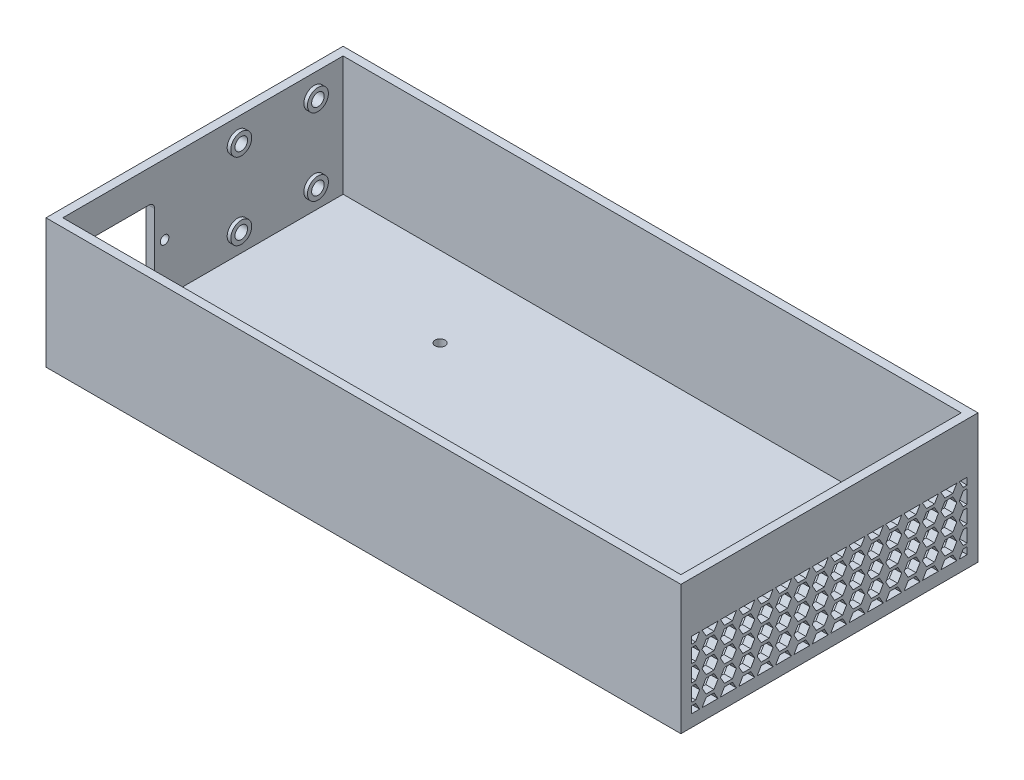
SolidWorks part; units mm, degrees
ref_plane "Front Plane" through (0, 0, 0) normal (0, 0, 1) x (1, 0, 0)
ref_plane "Top Plane" through (0, 0, 0) normal (0, 1, 0) x (1, 0, 0)
ref_plane "Right Plane" through (0, 0, 0) normal (1, 0, 0) x (0, 0, -1)
sketch "Sketch1" plane through (0, 0, 0) normal (0, 1, 0) x (1, 0, 0)
  line L0 (0, 1) -> (216, 1)
  line L1 (0, 0) -> (215, 0)
  line L3 (0, -115) -> (215, -115)
  line L4 (215, 0) -> (215, -115)
  line L5 (0, 0) -> (-41, 0)
  line L7 (0, -115) -> (-41, -115)
  line L8 (-41, 0) -> (-41, -115)
  line L9 (216, 1) -> (216, -116)
  line L10 (0, -116) -> (216, -116)
  line L11 (0, -116) -> (-42, -116)
  line L12 (-42, 1) -> (-42, -116)
  line L13 (0, 1) -> (-42, 1)
  line L14 (0, -119.5) -> (-45.5, -119.5)
  line L15 (-45.5, 4.5) -> (-45.5, -119.5)
  line L16 (0, 4.5) -> (-45.5, 4.5)
  line L17 (0, 4.5) -> (219.5, 4.5)
  line L18 (219.5, 4.5) -> (219.5, -119.5)
  line L19 (0, -119.5) -> (219.5, -119.5)
  dimension "D1" = 115
  dimension "D2" = 215
  dimension "D3" = 41
  dimension "D5" = 3.5
  dimension "D4" = 1
extrude "Boss-Extrude1" add sketch "Sketch1" against normal blind 4 contours L14 L15 L16 L17 L18 L19
extrude "Boss-Extrude2" add sketch "Sketch1<3>" along normal blind 50 contours L14 L19 L18 L17 L16 L15 L13 L0 L9 L10 L11 L12 region at (-22.75, 0, 116.5742)
sketch "Sketch1<3>" plane through (0, 0, 0) normal (0, 1, 0) x (1, 0, 0) same geometry as "Sketch1"
sketch "Sketch2" plane through (0, 0, 0) normal (0, 1, 0) x (1, 0, 0)
  line L0 (182, -32.5) -> (182, -82.5) construction
  line L1 (216, 1) -> (216, -116) construction
  circle A0 centre (32, -32.5) radius 2.1
  circle A1 centre (182, -32.5) radius 2.1
  circle A2 centre (182, -82.5) radius 2.1
  circle A3 centre (32, -82.5) radius 2.1
  point P4 (216, -57.5)
  point P11 (182, -57.5)
  dimension "D3" = 4.2
  dimension "D4" = 184
  dimension "D5" = 150
  dimension "D6" = 50
  dimension "D1" = 2
  dimension "D2" = 2
extrude "Cut-Extrude1" cut sketch "Sketch2" against normal through all
sketch "Sketch3" plane through (0, -4, 0) normal (0, -1, 0) x (1, 0, 0)
  line L0 (-33.5, 107.5) -> (207.5, 107.5) construction
  line L1 (-33.5, 107.5) -> (-33.5, 7.5) construction
  line L2 (-45.5, -4.5) -> (-45.5, 119.5) construction
  line L3 (-45.5, 119.5) -> (219.5, 119.5) construction
  line L4 (-45.5, -4.5) -> (219.5, -4.5) construction
  line L5 (219.5, -4.5) -> (219.5, 119.5) construction
  circle A0 centre (-33.5, 107.5) radius 7.5
  circle A1 centre (207.5, 107.5) radius 7.5
  circle A2 centre (207.5, 7.5) radius 7.5
  circle A3 centre (-33.5, 7.5) radius 7.5
  dimension "D4" = 15
  dimension "D3" = 90
  dimension "D5" = 12
  dimension "D6" = 12
  dimension "D7" = 12
  dimension "D8" = 12
  dimension "D1" = 2
  dimension "D2" = 2
extrude "Cut-Extrude2" cut sketch "Sketch3" against normal blind 1
sketch "Sketch5" plane through (-45.5, 0, 0) normal (-1, 0, 0) x (0, 0, 1)
  line L0 (91.5, 36.61) -> (91.5, 5) construction
  line L1 (80.105, 36.61) -> (102.895, 36.61)
  line L2 (77.695, 34.2) -> (77.695, 7.41)
  line L3 (80.105, 5) -> (102.895, 5)
  line L4 (105.305, 34.2) -> (105.305, 7.41)
  line L5 (-1, 0) -> (116, 0) construction
  line L6 (119.5, -4) -> (119.5, 50) construction
  circle A0 centre (73.5, 20.805) radius 1.8
  circle A1 centre (109.5, 20.805) radius 1.8
  arc A2 (77.695, 7.41) -> (80.105, 5) centre (80.105, 7.41) ccw
  arc A3 (102.895, 5) -> (105.305, 7.41) centre (102.895, 7.41) ccw
  arc A4 (102.895, 36.61) -> (105.305, 34.2) centre (102.895, 34.2) cw
  arc A5 (80.105, 36.61) -> (77.695, 34.2) centre (80.105, 34.2) ccw
  point P10 (91.5, 20.805)
  point P13 (77.695, 5)
  point P16 (105.305, 5)
  point P19 (105.305, 36.61)
  dimension "D4" = 3.6
  dimension "D5" = 2.41
  dimension "D1" = 27.61
  dimension "D2" = 31.61
  dimension "D3" = 36
  dimension "D6" = 5
  dimension "D7" = 10
extrude "Cut-Extrude3" cut sketch "Sketch5" against normal up to next
sketch "Sketch6" plane through (219.5, 0, 0) normal (1, 0, 0) x (0, 0, -1)
  line L21 (1, 0) -> (-116, 0) construction
  line L22 (-115, 29) -> (0, 29)
  line L23 (-115, 29) -> (-115, 1)
  line L24 (-115, 1) -> (0, 1)
  line L25 (0, 29) -> (0, 1)
  line L26 (1, 50) -> (1, 0) construction
  line L27 (-116, 50) -> (-116, 0) construction
  line L28 (-104.0136, 29) -> (-105.6735, 31.875)
  line L29 (-111.6802, 29) -> (-113.3401, 31.875)
  line L30 (-113.3401, 31.875) -> (-116.6599, 31.875)
  line L31 (-116.6599, 31.875) -> (-118.3198, 29)
  line L32 (-118.3198, 29) -> (-116.6599, 26.125)
  line L33 (-116.6599, 26.125) -> (-113.3401, 26.125)
  line L34 (-113.3401, 26.125) -> (-111.6802, 29)
  line L35 (-105.6735, 31.875) -> (-108.9932, 31.875)
  line L36 (-108.9932, 31.875) -> (-110.6531, 29)
  line L37 (-110.6531, 29) -> (-108.9932, 26.125)
  line L38 (-108.9932, 26.125) -> (-105.6735, 26.125)
  line L39 (-105.6735, 26.125) -> (-104.0136, 29)
  line L40 (-96.3469, 29) -> (-98.0068, 31.875)
  line L41 (-98.0068, 31.875) -> (-101.3265, 31.875)
  line L42 (-101.3265, 31.875) -> (-102.9864, 29)
  line L43 (-102.9864, 29) -> (-101.3265, 26.125)
  line L44 (-101.3265, 26.125) -> (-98.0068, 26.125)
  line L45 (-98.0068, 26.125) -> (-96.3469, 29)
  line L46 (-88.6802, 29) -> (-90.3401, 31.875)
  line L47 (-90.3401, 31.875) -> (-93.6599, 31.875)
  line L48 (-93.6599, 31.875) -> (-95.3198, 29)
  line L49 (-95.3198, 29) -> (-93.6599, 26.125)
  line L50 (-93.6599, 26.125) -> (-90.3401, 26.125)
  line L51 (-90.3401, 26.125) -> (-88.6802, 29)
  line L52 (-81.0136, 29) -> (-82.6735, 31.875)
  line L53 (-82.6735, 31.875) -> (-85.9932, 31.875)
  line L54 (-85.9932, 31.875) -> (-87.6531, 29)
  line L55 (-87.6531, 29) -> (-85.9932, 26.125)
  line L56 (-85.9932, 26.125) -> (-82.6735, 26.125)
  line L57 (-82.6735, 26.125) -> (-81.0136, 29)
  line L58 (-73.3469, 29) -> (-75.0068, 31.875)
  line L59 (-75.0068, 31.875) -> (-78.3265, 31.875)
  line L60 (-78.3265, 31.875) -> (-79.9864, 29)
  line L61 (-79.9864, 29) -> (-78.3265, 26.125)
  line L62 (-78.3265, 26.125) -> (-75.0068, 26.125)
  line L63 (-75.0068, 26.125) -> (-73.3469, 29)
  line L64 (-65.6802, 29) -> (-67.3401, 31.875)
  line L65 (-67.3401, 31.875) -> (-70.6599, 31.875)
  line L66 (-70.6599, 31.875) -> (-72.3198, 29)
  line L67 (-72.3198, 29) -> (-70.6599, 26.125)
  line L68 (-70.6599, 26.125) -> (-67.3401, 26.125)
  line L69 (-67.3401, 26.125) -> (-65.6802, 29)
  line L70 (-58.0136, 29) -> (-59.6735, 31.875)
  line L71 (-59.6735, 31.875) -> (-62.9932, 31.875)
  line L72 (-62.9932, 31.875) -> (-64.6531, 29)
  line L73 (-64.6531, 29) -> (-62.9932, 26.125)
  line L74 (-62.9932, 26.125) -> (-59.6735, 26.125)
  line L75 (-59.6735, 26.125) -> (-58.0136, 29)
  line L76 (-50.3469, 29) -> (-52.0068, 31.875)
  line L77 (-52.0068, 31.875) -> (-55.3265, 31.875)
  line L78 (-55.3265, 31.875) -> (-56.9864, 29)
  line L79 (-56.9864, 29) -> (-55.3265, 26.125)
  line L80 (-55.3265, 26.125) -> (-52.0068, 26.125)
  line L81 (-52.0068, 26.125) -> (-50.3469, 29)
  line L82 (-42.6802, 29) -> (-44.3401, 31.875)
  line L83 (-44.3401, 31.875) -> (-47.6599, 31.875)
  line L84 (-47.6599, 31.875) -> (-49.3198, 29)
  line L85 (-49.3198, 29) -> (-47.6599, 26.125)
  line L86 (-47.6599, 26.125) -> (-44.3401, 26.125)
  line L87 (-44.3401, 26.125) -> (-42.6802, 29)
  line L88 (-35.0136, 29) -> (-36.6735, 31.875)
  line L89 (-36.6735, 31.875) -> (-39.9932, 31.875)
  line L90 (-39.9932, 31.875) -> (-41.6531, 29)
  line L91 (-41.6531, 29) -> (-39.9932, 26.125)
  line L92 (-39.9932, 26.125) -> (-36.6735, 26.125)
  line L93 (-36.6735, 26.125) -> (-35.0136, 29)
  line L94 (-27.3469, 29) -> (-29.0068, 31.875)
  line L95 (-29.0068, 31.875) -> (-32.3265, 31.875)
  line L96 (-32.3265, 31.875) -> (-33.9864, 29)
  line L97 (-33.9864, 29) -> (-32.3265, 26.125)
  line L98 (-32.3265, 26.125) -> (-29.0068, 26.125)
  line L99 (-29.0068, 26.125) -> (-27.3469, 29)
  line L100 (-19.6802, 29) -> (-21.3401, 31.875)
  line L101 (-21.3401, 31.875) -> (-24.6599, 31.875)
  line L102 (-24.6599, 31.875) -> (-26.3198, 29)
  line L103 (-26.3198, 29) -> (-24.6599, 26.125)
  line L104 (-24.6599, 26.125) -> (-21.3401, 26.125)
  line L105 (-21.3401, 26.125) -> (-19.6802, 29)
  line L106 (-12.0136, 29) -> (-13.6735, 31.875)
  line L107 (-13.6735, 31.875) -> (-16.9932, 31.875)
  line L108 (-16.9932, 31.875) -> (-18.6531, 29)
  line L109 (-18.6531, 29) -> (-16.9932, 26.125)
  line L110 (-16.9932, 26.125) -> (-13.6735, 26.125)
  line L111 (-13.6735, 26.125) -> (-12.0136, 29)
  line L112 (-4.3469, 29) -> (-6.0068, 31.875)
  line L113 (-6.0068, 31.875) -> (-9.3265, 31.875)
  line L114 (-9.3265, 31.875) -> (-10.9864, 29)
  line L115 (-10.9864, 29) -> (-9.3265, 26.125)
  line L116 (-9.3265, 26.125) -> (-6.0068, 26.125)
  line L117 (-6.0068, 26.125) -> (-4.3469, 29)
  line L118 (3.3198, 29) -> (1.6599, 31.875)
  line L119 (1.6599, 31.875) -> (-1.6599, 31.875)
  line L120 (-1.6599, 31.875) -> (-3.3198, 29)
  line L121 (-3.3198, 29) -> (-1.6599, 26.125)
  line L122 (-1.6599, 26.125) -> (1.6599, 26.125)
  line L123 (1.6599, 26.125) -> (3.3198, 29)
  line L124 (-104.0136, 22) -> (-105.6735, 24.875)
  line L125 (-105.6735, 24.875) -> (-108.9932, 24.875)
  line L126 (-108.9932, 24.875) -> (-110.6531, 22)
  line L127 (-110.6531, 22) -> (-108.9932, 19.125)
  line L128 (-108.9932, 19.125) -> (-105.6735, 19.125)
  line L129 (-105.6735, 19.125) -> (-104.0136, 22)
  line L130 (-96.3469, 22) -> (-98.0068, 24.875)
  line L131 (-98.0068, 24.875) -> (-101.3265, 24.875)
  line L132 (-101.3265, 24.875) -> (-102.9864, 22)
  line L133 (-102.9864, 22) -> (-101.3265, 19.125)
  line L134 (-101.3265, 19.125) -> (-98.0068, 19.125)
  line L135 (-98.0068, 19.125) -> (-96.3469, 22)
  line L136 (-88.6802, 22) -> (-90.3401, 24.875)
  line L137 (-90.3401, 24.875) -> (-93.6599, 24.875)
  line L138 (-93.6599, 24.875) -> (-95.3198, 22)
  line L139 (-95.3198, 22) -> (-93.6599, 19.125)
  line L140 (-93.6599, 19.125) -> (-90.3401, 19.125)
  line L141 (-90.3401, 19.125) -> (-88.6802, 22)
  line L142 (-81.0136, 22) -> (-82.6735, 24.875)
  line L143 (-82.6735, 24.875) -> (-85.9932, 24.875)
  line L144 (-85.9932, 24.875) -> (-87.6531, 22)
  line L145 (-87.6531, 22) -> (-85.9932, 19.125)
  line L146 (-85.9932, 19.125) -> (-82.6735, 19.125)
  line L147 (-82.6735, 19.125) -> (-81.0136, 22)
  line L148 (-73.3469, 22) -> (-75.0068, 24.875)
  line L149 (-75.0068, 24.875) -> (-78.3265, 24.875)
  line L150 (-78.3265, 24.875) -> (-79.9864, 22)
  line L151 (-79.9864, 22) -> (-78.3265, 19.125)
  line L152 (-78.3265, 19.125) -> (-75.0068, 19.125)
  line L153 (-75.0068, 19.125) -> (-73.3469, 22)
  line L154 (-65.6802, 22) -> (-67.3401, 24.875)
  line L155 (-67.3401, 24.875) -> (-70.6599, 24.875)
  line L156 (-70.6599, 24.875) -> (-72.3198, 22)
  line L157 (-72.3198, 22) -> (-70.6599, 19.125)
  line L158 (-70.6599, 19.125) -> (-67.3401, 19.125)
  line L159 (-67.3401, 19.125) -> (-65.6802, 22)
  line L160 (-58.0136, 22) -> (-59.6735, 24.875)
  line L161 (-59.6735, 24.875) -> (-62.9932, 24.875)
  line L162 (-62.9932, 24.875) -> (-64.6531, 22)
  line L163 (-64.6531, 22) -> (-62.9932, 19.125)
  line L164 (-62.9932, 19.125) -> (-59.6735, 19.125)
  line L165 (-59.6735, 19.125) -> (-58.0136, 22)
  line L166 (-50.3469, 22) -> (-52.0068, 24.875)
  line L167 (-52.0068, 24.875) -> (-55.3265, 24.875)
  line L168 (-55.3265, 24.875) -> (-56.9864, 22)
  line L169 (-56.9864, 22) -> (-55.3265, 19.125)
  line L170 (-55.3265, 19.125) -> (-52.0068, 19.125)
  line L171 (-52.0068, 19.125) -> (-50.3469, 22)
  line L172 (-42.6802, 22) -> (-44.3401, 24.875)
  line L173 (-44.3401, 24.875) -> (-47.6599, 24.875)
  line L174 (-47.6599, 24.875) -> (-49.3198, 22)
  line L175 (-49.3198, 22) -> (-47.6599, 19.125)
  line L176 (-47.6599, 19.125) -> (-44.3401, 19.125)
  line L177 (-44.3401, 19.125) -> (-42.6802, 22)
  line L178 (-35.0136, 22) -> (-36.6735, 24.875)
  line L179 (-36.6735, 24.875) -> (-39.9932, 24.875)
  line L180 (-39.9932, 24.875) -> (-41.6531, 22)
  line L181 (-41.6531, 22) -> (-39.9932, 19.125)
  line L182 (-39.9932, 19.125) -> (-36.6735, 19.125)
  line L183 (-36.6735, 19.125) -> (-35.0136, 22)
  line L184 (-27.3469, 22) -> (-29.0068, 24.875)
  line L185 (-29.0068, 24.875) -> (-32.3265, 24.875)
  line L186 (-32.3265, 24.875) -> (-33.9864, 22)
  line L187 (-33.9864, 22) -> (-32.3265, 19.125)
  line L188 (-32.3265, 19.125) -> (-29.0068, 19.125)
  line L189 (-29.0068, 19.125) -> (-27.3469, 22)
  line L190 (-19.6802, 22) -> (-21.3401, 24.875)
  line L191 (-21.3401, 24.875) -> (-24.6599, 24.875)
  line L192 (-24.6599, 24.875) -> (-26.3198, 22)
  line L193 (-26.3198, 22) -> (-24.6599, 19.125)
  line L194 (-24.6599, 19.125) -> (-21.3401, 19.125)
  line L195 (-21.3401, 19.125) -> (-19.6802, 22)
  line L196 (-12.0136, 22) -> (-13.6735, 24.875)
  line L197 (-13.6735, 24.875) -> (-16.9932, 24.875)
  line L198 (-16.9932, 24.875) -> (-18.6531, 22)
  line L199 (-18.6531, 22) -> (-16.9932, 19.125)
  line L200 (-16.9932, 19.125) -> (-13.6735, 19.125)
  line L201 (-13.6735, 19.125) -> (-12.0136, 22)
  line L202 (-4.3469, 22) -> (-6.0068, 24.875)
  line L203 (-6.0068, 24.875) -> (-9.3265, 24.875)
  line L204 (-9.3265, 24.875) -> (-10.9864, 22)
  line L205 (-10.9864, 22) -> (-9.3265, 19.125)
  line L206 (-9.3265, 19.125) -> (-6.0068, 19.125)
  line L207 (-6.0068, 19.125) -> (-4.3469, 22)
  line L208 (3.3198, 22) -> (1.6599, 24.875)
  line L209 (1.6599, 24.875) -> (-1.6599, 24.875)
  line L210 (-1.6599, 24.875) -> (-3.3198, 22)
  line L211 (-3.3198, 22) -> (-1.6599, 19.125)
  line L212 (-1.6599, 19.125) -> (1.6599, 19.125)
  line L213 (1.6599, 19.125) -> (3.3198, 22)
  line L214 (-104.0136, 15) -> (-105.6735, 17.875)
  line L215 (-105.6735, 17.875) -> (-108.9932, 17.875)
  line L216 (-108.9932, 17.875) -> (-110.6531, 15)
  line L217 (-110.6531, 15) -> (-108.9932, 12.125)
  line L218 (-108.9932, 12.125) -> (-105.6735, 12.125)
  line L219 (-105.6735, 12.125) -> (-104.0136, 15)
  line L220 (-96.3469, 15) -> (-98.0068, 17.875)
  line L221 (-98.0068, 17.875) -> (-101.3265, 17.875)
  line L222 (-101.3265, 17.875) -> (-102.9864, 15)
  line L223 (-102.9864, 15) -> (-101.3265, 12.125)
  line L224 (-101.3265, 12.125) -> (-98.0068, 12.125)
  line L225 (-98.0068, 12.125) -> (-96.3469, 15)
  line L226 (-88.6802, 15) -> (-90.3401, 17.875)
  line L227 (-90.3401, 17.875) -> (-93.6599, 17.875)
  line L228 (-93.6599, 17.875) -> (-95.3198, 15)
  line L229 (-95.3198, 15) -> (-93.6599, 12.125)
  line L230 (-93.6599, 12.125) -> (-90.3401, 12.125)
  line L231 (-90.3401, 12.125) -> (-88.6802, 15)
  line L232 (-81.0136, 15) -> (-82.6735, 17.875)
  line L233 (-82.6735, 17.875) -> (-85.9932, 17.875)
  line L234 (-85.9932, 17.875) -> (-87.6531, 15)
  line L235 (-87.6531, 15) -> (-85.9932, 12.125)
  line L236 (-85.9932, 12.125) -> (-82.6735, 12.125)
  line L237 (-82.6735, 12.125) -> (-81.0136, 15)
  line L238 (-73.3469, 15) -> (-75.0068, 17.875)
  line L239 (-75.0068, 17.875) -> (-78.3265, 17.875)
  line L240 (-78.3265, 17.875) -> (-79.9864, 15)
  line L241 (-79.9864, 15) -> (-78.3265, 12.125)
  line L242 (-78.3265, 12.125) -> (-75.0068, 12.125)
  line L243 (-75.0068, 12.125) -> (-73.3469, 15)
  line L244 (-65.6802, 15) -> (-67.3401, 17.875)
  line L245 (-67.3401, 17.875) -> (-70.6599, 17.875)
  line L246 (-70.6599, 17.875) -> (-72.3198, 15)
  line L247 (-72.3198, 15) -> (-70.6599, 12.125)
  line L248 (-70.6599, 12.125) -> (-67.3401, 12.125)
  line L249 (-67.3401, 12.125) -> (-65.6802, 15)
  line L250 (-58.0136, 15) -> (-59.6735, 17.875)
  line L251 (-59.6735, 17.875) -> (-62.9932, 17.875)
  line L252 (-62.9932, 17.875) -> (-64.6531, 15)
  line L253 (-64.6531, 15) -> (-62.9932, 12.125)
  line L254 (-62.9932, 12.125) -> (-59.6735, 12.125)
  line L255 (-59.6735, 12.125) -> (-58.0136, 15)
  line L256 (-50.3469, 15) -> (-52.0068, 17.875)
  line L257 (-52.0068, 17.875) -> (-55.3265, 17.875)
  line L258 (-55.3265, 17.875) -> (-56.9864, 15)
  line L259 (-56.9864, 15) -> (-55.3265, 12.125)
  line L260 (-55.3265, 12.125) -> (-52.0068, 12.125)
  line L261 (-52.0068, 12.125) -> (-50.3469, 15)
  line L262 (-42.6802, 15) -> (-44.3401, 17.875)
  line L263 (-44.3401, 17.875) -> (-47.6599, 17.875)
  line L264 (-47.6599, 17.875) -> (-49.3198, 15)
  line L265 (-49.3198, 15) -> (-47.6599, 12.125)
  line L266 (-47.6599, 12.125) -> (-44.3401, 12.125)
  line L267 (-44.3401, 12.125) -> (-42.6802, 15)
  line L268 (-35.0136, 15) -> (-36.6735, 17.875)
  line L269 (-36.6735, 17.875) -> (-39.9932, 17.875)
  line L270 (-39.9932, 17.875) -> (-41.6531, 15)
  line L271 (-41.6531, 15) -> (-39.9932, 12.125)
  line L272 (-39.9932, 12.125) -> (-36.6735, 12.125)
  line L273 (-36.6735, 12.125) -> (-35.0136, 15)
  line L274 (-27.3469, 15) -> (-29.0068, 17.875)
  line L275 (-29.0068, 17.875) -> (-32.3265, 17.875)
  line L276 (-32.3265, 17.875) -> (-33.9864, 15)
  line L277 (-33.9864, 15) -> (-32.3265, 12.125)
  line L278 (-32.3265, 12.125) -> (-29.0068, 12.125)
  line L279 (-29.0068, 12.125) -> (-27.3469, 15)
  line L280 (-19.6802, 15) -> (-21.3401, 17.875)
  line L281 (-21.3401, 17.875) -> (-24.6599, 17.875)
  line L282 (-24.6599, 17.875) -> (-26.3198, 15)
  line L283 (-26.3198, 15) -> (-24.6599, 12.125)
  line L284 (-24.6599, 12.125) -> (-21.3401, 12.125)
  line L285 (-21.3401, 12.125) -> (-19.6802, 15)
  line L286 (-12.0136, 15) -> (-13.6735, 17.875)
  line L287 (-13.6735, 17.875) -> (-16.9932, 17.875)
  line L288 (-16.9932, 17.875) -> (-18.6531, 15)
  line L289 (-18.6531, 15) -> (-16.9932, 12.125)
  line L290 (-16.9932, 12.125) -> (-13.6735, 12.125)
  line L291 (-13.6735, 12.125) -> (-12.0136, 15)
  line L292 (-4.3469, 15) -> (-6.0068, 17.875)
  line L293 (-6.0068, 17.875) -> (-9.3265, 17.875)
  line L294 (-9.3265, 17.875) -> (-10.9864, 15)
  line L295 (-10.9864, 15) -> (-9.3265, 12.125)
  line L296 (-9.3265, 12.125) -> (-6.0068, 12.125)
  line L297 (-6.0068, 12.125) -> (-4.3469, 15)
  line L298 (3.3198, 15) -> (1.6599, 17.875)
  line L299 (1.6599, 17.875) -> (-1.6599, 17.875)
  line L300 (-1.6599, 17.875) -> (-3.3198, 15)
  line L301 (-3.3198, 15) -> (-1.6599, 12.125)
  line L302 (-1.6599, 12.125) -> (1.6599, 12.125)
  line L303 (1.6599, 12.125) -> (3.3198, 15)
  line L304 (-104.0136, 8) -> (-105.6735, 10.875)
  line L305 (-105.6735, 10.875) -> (-108.9932, 10.875)
  line L306 (-108.9932, 10.875) -> (-110.6531, 8)
  line L307 (-110.6531, 8) -> (-108.9932, 5.125)
  line L308 (-108.9932, 5.125) -> (-105.6735, 5.125)
  line L309 (-105.6735, 5.125) -> (-104.0136, 8)
  line L310 (-96.3469, 8) -> (-98.0068, 10.875)
  line L311 (-98.0068, 10.875) -> (-101.3265, 10.875)
  line L312 (-101.3265, 10.875) -> (-102.9864, 8)
  line L313 (-102.9864, 8) -> (-101.3265, 5.125)
  line L314 (-101.3265, 5.125) -> (-98.0068, 5.125)
  line L315 (-98.0068, 5.125) -> (-96.3469, 8)
  line L316 (-88.6802, 8) -> (-90.3401, 10.875)
  line L317 (-90.3401, 10.875) -> (-93.6599, 10.875)
  line L318 (-93.6599, 10.875) -> (-95.3198, 8)
  line L319 (-95.3198, 8) -> (-93.6599, 5.125)
  line L320 (-93.6599, 5.125) -> (-90.3401, 5.125)
  line L321 (-90.3401, 5.125) -> (-88.6802, 8)
  line L322 (-81.0136, 8) -> (-82.6735, 10.875)
  line L323 (-82.6735, 10.875) -> (-85.9932, 10.875)
  line L324 (-85.9932, 10.875) -> (-87.6531, 8)
  line L325 (-87.6531, 8) -> (-85.9932, 5.125)
  line L326 (-85.9932, 5.125) -> (-82.6735, 5.125)
  line L327 (-82.6735, 5.125) -> (-81.0136, 8)
  line L328 (-73.3469, 8) -> (-75.0068, 10.875)
  line L329 (-75.0068, 10.875) -> (-78.3265, 10.875)
  line L330 (-78.3265, 10.875) -> (-79.9864, 8)
  line L331 (-79.9864, 8) -> (-78.3265, 5.125)
  line L332 (-78.3265, 5.125) -> (-75.0068, 5.125)
  line L333 (-75.0068, 5.125) -> (-73.3469, 8)
  line L334 (-65.6802, 8) -> (-67.3401, 10.875)
  line L335 (-67.3401, 10.875) -> (-70.6599, 10.875)
  line L336 (-70.6599, 10.875) -> (-72.3198, 8)
  line L337 (-72.3198, 8) -> (-70.6599, 5.125)
  line L338 (-70.6599, 5.125) -> (-67.3401, 5.125)
  line L339 (-67.3401, 5.125) -> (-65.6802, 8)
  line L340 (-58.0136, 8) -> (-59.6735, 10.875)
  line L341 (-59.6735, 10.875) -> (-62.9932, 10.875)
  line L342 (-62.9932, 10.875) -> (-64.6531, 8)
  line L343 (-64.6531, 8) -> (-62.9932, 5.125)
  line L344 (-62.9932, 5.125) -> (-59.6735, 5.125)
  line L345 (-59.6735, 5.125) -> (-58.0136, 8)
  line L346 (-50.3469, 8) -> (-52.0068, 10.875)
  line L347 (-52.0068, 10.875) -> (-55.3265, 10.875)
  line L348 (-55.3265, 10.875) -> (-56.9864, 8)
  line L349 (-56.9864, 8) -> (-55.3265, 5.125)
  line L350 (-55.3265, 5.125) -> (-52.0068, 5.125)
  line L351 (-52.0068, 5.125) -> (-50.3469, 8)
  line L352 (-42.6802, 8) -> (-44.3401, 10.875)
  line L353 (-44.3401, 10.875) -> (-47.6599, 10.875)
  line L354 (-47.6599, 10.875) -> (-49.3198, 8)
  line L355 (-49.3198, 8) -> (-47.6599, 5.125)
  line L356 (-47.6599, 5.125) -> (-44.3401, 5.125)
  line L357 (-44.3401, 5.125) -> (-42.6802, 8)
  line L358 (-35.0136, 8) -> (-36.6735, 10.875)
  line L359 (-36.6735, 10.875) -> (-39.9932, 10.875)
  line L360 (-39.9932, 10.875) -> (-41.6531, 8)
  line L361 (-41.6531, 8) -> (-39.9932, 5.125)
  line L362 (-39.9932, 5.125) -> (-36.6735, 5.125)
  line L363 (-36.6735, 5.125) -> (-35.0136, 8)
  line L364 (-27.3469, 8) -> (-29.0068, 10.875)
  line L365 (-29.0068, 10.875) -> (-32.3265, 10.875)
  line L366 (-32.3265, 10.875) -> (-33.9864, 8)
  line L367 (-33.9864, 8) -> (-32.3265, 5.125)
  line L368 (-32.3265, 5.125) -> (-29.0068, 5.125)
  line L369 (-29.0068, 5.125) -> (-27.3469, 8)
  line L370 (-19.6802, 8) -> (-21.3401, 10.875)
  line L371 (-21.3401, 10.875) -> (-24.6599, 10.875)
  line L372 (-24.6599, 10.875) -> (-26.3198, 8)
  line L373 (-26.3198, 8) -> (-24.6599, 5.125)
  line L374 (-24.6599, 5.125) -> (-21.3401, 5.125)
  line L375 (-21.3401, 5.125) -> (-19.6802, 8)
  line L376 (-12.0136, 8) -> (-13.6735, 10.875)
  line L377 (-13.6735, 10.875) -> (-16.9932, 10.875)
  line L378 (-16.9932, 10.875) -> (-18.6531, 8)
  line L379 (-18.6531, 8) -> (-16.9932, 5.125)
  line L380 (-16.9932, 5.125) -> (-13.6735, 5.125)
  line L381 (-13.6735, 5.125) -> (-12.0136, 8)
  line L382 (-4.3469, 8) -> (-6.0068, 10.875)
  line L383 (-6.0068, 10.875) -> (-9.3265, 10.875)
  line L384 (-9.3265, 10.875) -> (-10.9864, 8)
  line L385 (-10.9864, 8) -> (-9.3265, 5.125)
  line L386 (-9.3265, 5.125) -> (-6.0068, 5.125)
  line L387 (-6.0068, 5.125) -> (-4.3469, 8)
  line L388 (3.3198, 8) -> (1.6599, 10.875)
  line L389 (1.6599, 10.875) -> (-1.6599, 10.875)
  line L390 (-1.6599, 10.875) -> (-3.3198, 8)
  line L391 (-3.3198, 8) -> (-1.6599, 5.125)
  line L392 (-1.6599, 5.125) -> (1.6599, 5.125)
  line L393 (1.6599, 5.125) -> (3.3198, 8)
  line L394 (-111.6802, 22) -> (-113.3401, 24.875)
  line L395 (-113.3401, 24.875) -> (-116.6599, 24.875)
  line L396 (-116.6599, 24.875) -> (-118.3198, 22)
  line L397 (-118.3198, 22) -> (-116.6599, 19.125)
  line L398 (-116.6599, 19.125) -> (-113.3401, 19.125)
  line L399 (-113.3401, 19.125) -> (-111.6802, 22)
  line L400 (-111.6802, 15) -> (-113.3401, 17.875)
  line L401 (-113.3401, 17.875) -> (-116.6599, 17.875)
  line L402 (-116.6599, 17.875) -> (-118.3198, 15)
  line L403 (-118.3198, 15) -> (-116.6599, 12.125)
  line L404 (-116.6599, 12.125) -> (-113.3401, 12.125)
  line L405 (-113.3401, 12.125) -> (-111.6802, 15)
  line L406 (-111.6802, 8) -> (-113.3401, 10.875)
  line L407 (-113.3401, 10.875) -> (-116.6599, 10.875)
  line L408 (-116.6599, 10.875) -> (-118.3198, 8)
  line L409 (-118.3198, 8) -> (-116.6599, 5.125)
  line L410 (-116.6599, 5.125) -> (-113.3401, 5.125)
  line L411 (-113.3401, 5.125) -> (-111.6802, 8)
  line L412 (-111.6802, 29) -> (-104.0136, 29) construction
  line L413 (-111.6802, 29) -> (-111.6802, 22) construction
  line L414 (-111.6802, 1) -> (-113.3401, 3.875)
  line L415 (-113.3401, 3.875) -> (-116.6599, 3.875)
  line L416 (-116.6599, 3.875) -> (-118.3198, 1)
  line L417 (-118.3198, 1) -> (-116.6599, -1.875)
  line L418 (-116.6599, -1.875) -> (-113.3401, -1.875)
  line L419 (-113.3401, -1.875) -> (-111.6802, 1)
  line L420 (-104.0136, 1) -> (-105.6735, 3.875)
  line L421 (-105.6735, 3.875) -> (-108.9932, 3.875)
  line L422 (-108.9932, 3.875) -> (-110.6531, 1)
  line L423 (-110.6531, 1) -> (-108.9932, -1.875)
  line L424 (-108.9932, -1.875) -> (-105.6735, -1.875)
  line L425 (-105.6735, -1.875) -> (-104.0136, 1)
  line L426 (-96.3469, 1) -> (-98.0068, 3.875)
  line L427 (-98.0068, 3.875) -> (-101.3265, 3.875)
  line L428 (-101.3265, 3.875) -> (-102.9864, 1)
  line L429 (-102.9864, 1) -> (-101.3265, -1.875)
  line L430 (-101.3265, -1.875) -> (-98.0068, -1.875)
  line L431 (-98.0068, -1.875) -> (-96.3469, 1)
  line L432 (-88.6802, 1) -> (-90.3401, 3.875)
  line L433 (-90.3401, 3.875) -> (-93.6599, 3.875)
  line L434 (-93.6599, 3.875) -> (-95.3198, 1)
  line L435 (-95.3198, 1) -> (-93.6599, -1.875)
  line L436 (-93.6599, -1.875) -> (-90.3401, -1.875)
  line L437 (-90.3401, -1.875) -> (-88.6802, 1)
  line L438 (-81.0136, 1) -> (-82.6735, 3.875)
  line L439 (-82.6735, 3.875) -> (-85.9932, 3.875)
  line L440 (-85.9932, 3.875) -> (-87.6531, 1)
  line L441 (-87.6531, 1) -> (-85.9932, -1.875)
  line L442 (-85.9932, -1.875) -> (-82.6735, -1.875)
  line L443 (-82.6735, -1.875) -> (-81.0136, 1)
  line L444 (-73.3469, 1) -> (-75.0068, 3.875)
  line L445 (-75.0068, 3.875) -> (-78.3265, 3.875)
  line L446 (-78.3265, 3.875) -> (-79.9864, 1)
  line L447 (-79.9864, 1) -> (-78.3265, -1.875)
  line L448 (-78.3265, -1.875) -> (-75.0068, -1.875)
  line L449 (-75.0068, -1.875) -> (-73.3469, 1)
  line L450 (-65.6802, 1) -> (-67.3401, 3.875)
  line L451 (-67.3401, 3.875) -> (-70.6599, 3.875)
  line L452 (-70.6599, 3.875) -> (-72.3198, 1)
  line L453 (-72.3198, 1) -> (-70.6599, -1.875)
  line L454 (-70.6599, -1.875) -> (-67.3401, -1.875)
  line L455 (-67.3401, -1.875) -> (-65.6802, 1)
  line L456 (-58.0136, 1) -> (-59.6735, 3.875)
  line L457 (-59.6735, 3.875) -> (-62.9932, 3.875)
  line L458 (-62.9932, 3.875) -> (-64.6531, 1)
  line L459 (-64.6531, 1) -> (-62.9932, -1.875)
  line L460 (-62.9932, -1.875) -> (-59.6735, -1.875)
  line L461 (-59.6735, -1.875) -> (-58.0136, 1)
  line L462 (-50.3469, 1) -> (-52.0068, 3.875)
  line L463 (-52.0068, 3.875) -> (-55.3265, 3.875)
  line L464 (-55.3265, 3.875) -> (-56.9864, 1)
  line L465 (-56.9864, 1) -> (-55.3265, -1.875)
  line L466 (-55.3265, -1.875) -> (-52.0068, -1.875)
  line L467 (-52.0068, -1.875) -> (-50.3469, 1)
  line L468 (-42.6802, 1) -> (-44.3401, 3.875)
  line L469 (-44.3401, 3.875) -> (-47.6599, 3.875)
  line L470 (-47.6599, 3.875) -> (-49.3198, 1)
  line L471 (-49.3198, 1) -> (-47.6599, -1.875)
  line L472 (-47.6599, -1.875) -> (-44.3401, -1.875)
  line L473 (-44.3401, -1.875) -> (-42.6802, 1)
  line L474 (-35.0136, 1) -> (-36.6735, 3.875)
  line L475 (-36.6735, 3.875) -> (-39.9932, 3.875)
  line L476 (-39.9932, 3.875) -> (-41.6531, 1)
  line L477 (-41.6531, 1) -> (-39.9932, -1.875)
  line L478 (-39.9932, -1.875) -> (-36.6735, -1.875)
  line L479 (-36.6735, -1.875) -> (-35.0136, 1)
  line L480 (-27.3469, 1) -> (-29.0068, 3.875)
  line L481 (-29.0068, 3.875) -> (-32.3265, 3.875)
  line L482 (-32.3265, 3.875) -> (-33.9864, 1)
  line L483 (-33.9864, 1) -> (-32.3265, -1.875)
  line L484 (-32.3265, -1.875) -> (-29.0068, -1.875)
  line L485 (-29.0068, -1.875) -> (-27.3469, 1)
  line L486 (-19.6802, 1) -> (-21.3401, 3.875)
  line L487 (-21.3401, 3.875) -> (-24.6599, 3.875)
  line L488 (-24.6599, 3.875) -> (-26.3198, 1)
  line L489 (-26.3198, 1) -> (-24.6599, -1.875)
  line L490 (-24.6599, -1.875) -> (-21.3401, -1.875)
  line L491 (-21.3401, -1.875) -> (-19.6802, 1)
  line L492 (-12.0136, 1) -> (-13.6735, 3.875)
  line L493 (-13.6735, 3.875) -> (-16.9932, 3.875)
  line L494 (-16.9932, 3.875) -> (-18.6531, 1)
  line L495 (-18.6531, 1) -> (-16.9932, -1.875)
  line L496 (-16.9932, -1.875) -> (-13.6735, -1.875)
  line L497 (-13.6735, -1.875) -> (-12.0136, 1)
  line L498 (-4.3469, 1) -> (-6.0068, 3.875)
  line L499 (-6.0068, 3.875) -> (-9.3265, 3.875)
  line L500 (-9.3265, 3.875) -> (-10.9864, 1)
  line L501 (-10.9864, 1) -> (-9.3265, -1.875)
  line L502 (-9.3265, -1.875) -> (-6.0068, -1.875)
  line L503 (-6.0068, -1.875) -> (-4.3469, 1)
  line L504 (3.3198, 1) -> (1.6599, 3.875)
  line L505 (1.6599, 3.875) -> (-1.6599, 3.875)
  line L506 (-1.6599, 3.875) -> (-3.3198, 1)
  line L507 (-3.3198, 1) -> (-1.6599, -1.875)
  line L508 (-1.6599, -1.875) -> (1.6599, -1.875)
  line L509 (1.6599, -1.875) -> (3.3198, 1)
  circle A2 centre (-115, 29) radius 2.875 construction
  point P11 (0, 10.875)
  point P20 (0, 0)
  point P399 (0, 0)
  point P402 (-1.6812, 3.912)
  dimension "D1" = 1
  dimension "D2" = 1
  dimension "D3" = 1
  dimension "D4" = 28
  dimension "D7" = 90
  dimension "D8" = 1.25
  dimension "D5" = 16
  dimension "D6" = 5
extrude "Cut-Extrude5" cut sketch "Sketch6" against normal blind 10 contours L33 L34 L22 L23 | L38 L39 L22 L37 | L44 L45 L22 L43 | L50 L51 L22 L49 | L56 L57 L22 L55 | L62 L63 L22 L61 | L68 L69 L22 L67 | L74 L75 L22 L73 | L80 L81 L22 L79 | L86 L87 L22 L85 | L92 L93 L22 L91 | L98 L99 L22 L97 | L104 L105 L22 L103 | L110 L111 L22 L109 | L116 L117 L22 L115 | L121 L122 L25 L22 | L211 L212 L25 L209 L210 | L301 L302 L25 L299 L300 | L391 L392 L25 L389 L390 | L505 L506 L24 L25 | L499 L500 L24 L498 | L493 L494 L24 L492 | L487 L488 L24 L486 | L481 L482 L24 L480 | L475 L476 L24 L474 | L469 L470 L24 L468 | L463 L464 L24 L462 | L457 L458 L24 L456 | L451 L452 L24 L450 | L445 L446 L24 L444 | L439 L440 L24 L438 | L433 L434 L24 L432 | L427 L428 L24 L426 | L421 L422 L24 L420 | L414 L415 L23 L24 | L410 L411 L406 L407 L23 | L404 L405 L400 L401 L23 | L398 L399 L394 L395 L23 | L128 L129 L124 L125 L126 L127 | L134 L135 L130 L131 L132 L133 | L140 L141 L136 L137 L138 L139 | L146 L147 L142 L143 L144 L145 | L152 L153 L148 L149 L150 L151 | L158 L159 L154 L155 L156 L157 | L164 L165 L160 L161 L162 L163 | L170 L171 L166 L167 L168 L169 | L176 L177 L172 L173 L174 L175 | L182 L183 L178 L179 L180 L181 | L188 L189 L184 L185 L186 L187 | L194 L195 L190 L191 L192 L193 | L200 L201 L196 L197 L198 L199 | L206 L207 L202 L203 L204 L205 | L296 L297 L292 L293 L294 L295 | L290 L291 L286 L287 L288 L289 | L380 L381 L376 L377 L378 L379 | L386 L387 L382 L383 L384 L385 | L374 L375 L370 L371 L372 L373 | L284 L285 L280 L281 L282 L283 | L278 L279 L274 L275 L276 L277 | L368 L369 L364 L365 L366 L367 | L362 L363 L358 L359 L360 L361 | L272 L273 L268 L269 L270 L271 | L266 L267 L262 L263 L264 L265 | L356 L357 L352 L353 L354 L355 | L350 L351 L346 L347 L348 L349 | L260 L261 L256 L257 L258 L259 | L254 L255 L250 L251 L252 L253 | L338 L339 L334 L335 L336 L337 | L248 L249 L244 L245 L246 L247 | L332 L333 L328 L329 L330 L331 | L242 L243 L238 L239 L240 L241 | L236 L237 L232 L233 L234 L235 | L326 L327 L322 L323 L324 L325 | L320 L321 L316 L317 L318 L319 | L230 L231 L226 L227 L228 L229 | L224 L225 L220 L221 L222 L223 | L314 L315 L310 L311 L312 L313 | L308 L309 L304 L305 L306 L307 | L218 L219 L214 L215 L216 L217 | L344 L345 L340 L341 L342 L343 | L192 L193 L194 L195 L190 L191 region at (219.5, 27.7222, 113.709) region at (219.5, 27.7222, 107.3333) region at (219.5, 22, 113.709) region at (219.5, 27.7222, 99.6667) region at (219.5, 15, 113.709) region at (219.5, 27.7222, 92) region at (219.5, 8, 113.709) region at (219.5, 27.7222, 84.3333) region at (219.5, 2.2778, 113.709) region at (219.5, 27.7222, 76.6667) region at (219.5, 2.2778, 107.3333) region at (219.5, 27.7222, 69) region at (219.5, 2.2778, 99.6667) region at (219.5, 27.7222, 61.3333) region at (219.5, 2.2778, 92) region at (219.5, 27.7222, 53.6667) region at (219.5, 2.2778, 84.3333) region at (219.5, 27.7222, 46) region at (219.5, 2.2778, 76.6667) region at (219.5, 27.7222, 38.3333) region at (219.5, 2.2778, 69) region at (219.5, 27.7222, 30.6667) region at (219.5, 2.2778, 61.3333) region at (219.5, 27.7222, 23) region at (219.5, 2.2778, 53.6667) region at (219.5, 27.7222, 15.3333) region at (219.5, 2.2778, 46) region at (219.5, 27.7222, 7.6667) region at (219.5, 2.2778, 38.3333) region at (219.5, 27.7222, 1.291) region at (219.5, 2.2778, 30.6667) region at (219.5, 22, 1.291) region at (219.5, 2.2778, 23) region at (219.5, 15, 1.291) region at (219.5, 2.2778, 15.3333) region at (219.5, 8, 1.291) region at (219.5, 2.2778, 7.6667) region at (219.5, 2.2778, 1.291) region at (219.5, 22, 107.3333) region at (219.5, 22, 99.6667) region at (219.5, 22, 92) region at (219.5, 22, 84.3333) region at (219.5, 22, 76.6667) region at (219.5, 22, 69) region at (219.5, 22, 61.3333) region at (219.5, 22, 53.6667) region at (219.5, 22, 46) region at (219.5, 22, 38.3333) region at (219.5, 22, 30.6667) region at (219.5, 22, 23) region at (219.5, 22, 15.3333) region at (219.5, 22, 7.6667) region at (219.5, 15, 107.3333) region at (219.5, 15, 99.6667) region at (219.5, 15, 92) region at (219.5, 15, 84.3333) region at (219.5, 15, 76.6667) region at (219.5, 15, 69) region at (219.5, 15, 61.3333) region at (219.5, 15, 53.6667)
sketch "Sketch8" plane through (-45.5, 0, 0) normal (-1, 0, 0) x (0, 0, 1)
  line L0 (11, 41) -> (43, 41) construction
  line L1 (11, 41) -> (11, 9) construction
  line L2 (-1, 50) -> (-1, 0) construction
  circle A0 centre (11, 41) radius 2.625
  circle A1 centre (43, 41) radius 2.625
  circle A2 centre (43, 9) radius 2.625
  circle A3 centre (11, 9) radius 2.625
  point P4 (11, 25)
  point P14 (-1, 25)
  dimension "D1" = 5.25
  dimension "D4" = 90
  dimension "D5" = 32
  dimension "D6" = 32
  dimension "D7" = 12
  dimension "D2" = 2
  dimension "D3" = 2
extrude "Cut-Extrude6" cut sketch "Sketch8" against normal blind 10
sketch "Sketch10" plane through (-42, 0, 0) normal (1, 0, 0) x (0, 0, -1)
  line L0 (-43, 41) -> (-11, 41) construction
  line L1 (-43, 41) -> (-43, 9) construction
  circle A0 centre (-43, 41) radius 4.375
  circle A1 centre (-11, 41) radius 4.375
  circle A2 centre (-11, 9) radius 4.375
  circle A3 centre (-43, 9) radius 4.375
  circle A7 centre (-43, 41) radius 2.625 construction
  circle A10 centre (-43, 41) radius 2.625
  circle A11 centre (-11, 41) radius 2.625
  circle A12 centre (-11, 9) radius 2.625
  circle A13 centre (-43, 9) radius 2.625
  point P3 (0, 0)
  point P4 (0, 0)
  point P6 (-43, 41)
  dimension "D4" = 1.75
  dimension "D3" = 90
  dimension "D1" = 2
  dimension "D2" = 2
extrude "Boss-Extrude3" add sketch "Sketch10" along normal blind 1.5
